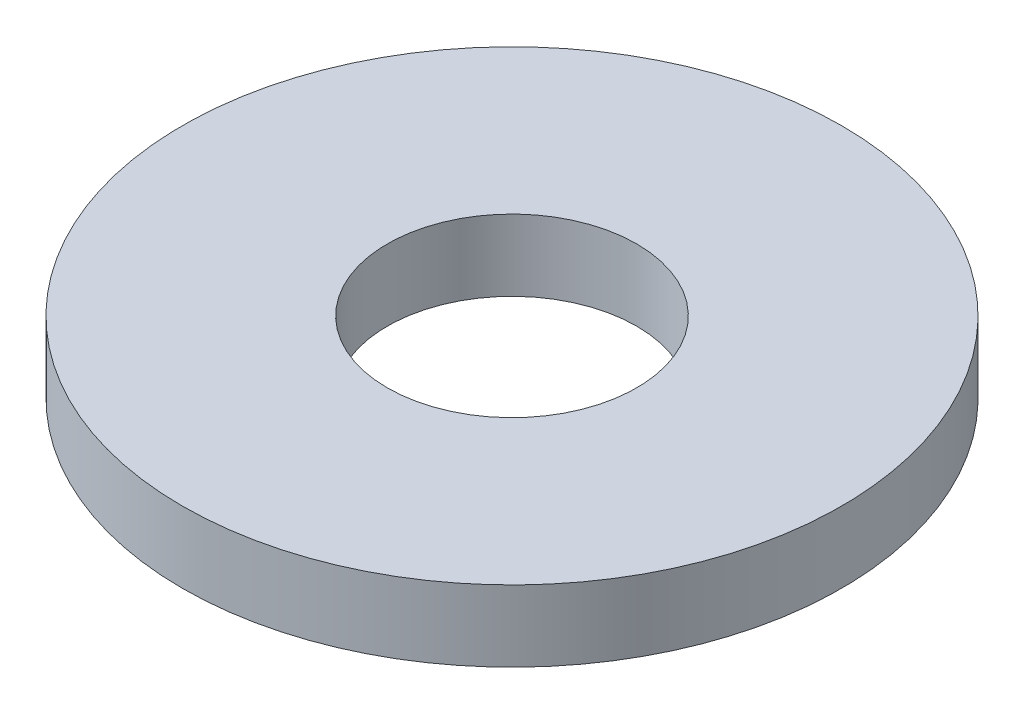
SolidWorks part; units mm, degrees
ref_plane "Front Plane" through (0, 0, 0) normal (0, 0, 1) x (1, 0, 0)
ref_plane "Top Plane" through (0, 0, 0) normal (0, 1, 0) x (1, 0, 0)
ref_plane "Right Plane" through (0, 0, 0) normal (1, 0, 0) x (0, 0, -1)
sketch "Sketch1" plane through (0, 0, 0) normal (0, 1, 0) x (1, 0, 0)
  circle A0 centre (0, 0) radius 92.5
  dimension "FLANGE_OD" = 185
extrude "Boss-Extrude1" add sketch "Sketch1" along normal blind 20
sketch "Sketch2" plane through (0, 0, 0) normal (0, 1, 0) x (1, 0, 0)
  circle A0 centre (0, 0) radius 35
  dimension "BORE_D" = 70
extrude "Cut-Extrude1" cut sketch "Sketch2" along normal through all
sketch "Sketch3" plane through (0, 20, 0) normal (0, 1, 0) x (1, 0, 0)
  circle A0 centre (0, 0) radius 23.4909 construction
  circle A1 centre (-23.4909, 0) radius 5.2457
  dimension "BOLT_D" = 10.4914
  dimension "BOLT_PCD" = 46.9817
extrude "Cut-Extrude2" cut sketch "Sketch3" against normal blind 18.0879 rebuild error yes
pattern_circular "CirPattern1" count 5 over 360 rebuild error yes
